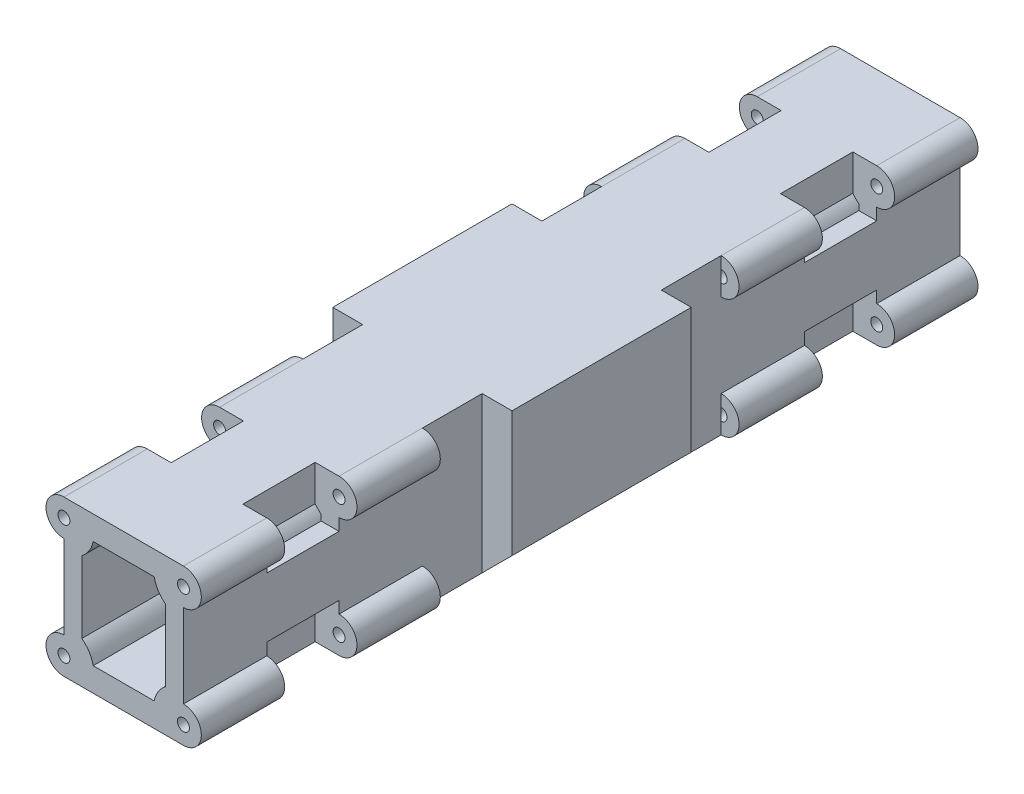
SolidWorks part; units mm, degrees
material "ABS"
ref_plane "Спереди" through (0, 0, 0) normal (0, 0, 1) x (1, 0, 0)
ref_plane "Сверху" through (0, 0, 0) normal (0, 1, 0) x (1, 0, 0)
ref_plane "Справа" through (0, 0, 0) normal (1, 0, 0) x (0, 0, -1)
sketch "Эскиз1" plane through (0, 0, 0) normal (0, 0, 1) x (1, 0, 0)
  line L0 (0, 30.7154) -> (0, -31.2898) construction
  line L2 (15, -13.2872) -> (-15, -13.2872)
  line L3 (15, -13.2872) -> (15, 12.7128)
  line L4 (15, 12.7128) -> (-15, 12.7128)
  line L5 (-15, -13.2872) -> (-15, 12.7128)
  line L6 (15, -13.2872) -> (-15, 12.7128) construction
  line L7 (15, 12.7128) -> (-15, -13.2872) construction
  point P3 (0, -0.2872)
  dimension "D1" = 30
  dimension "D2" = 26
extrude "Бобышка-Вытянуть1" add sketch "Эскиз1" along normal mid plane 130
sketch "Эскиз7" plane through (0, 0, 65) normal (0, 0, 1) x (1, 0, 0)
  line L1 (-15, -13.2872) -> (-10, -13.2872)
  line L2 (-15, -13.2872) -> (-15, 12.7128)
  line L3 (-15, 12.7128) -> (-10, 12.7128)
  line L4 (-10, -13.2872) -> (-10, 12.7128)
  dimension "D1" = 26
  dimension "D2" = 5
extrude "Вырез-Вытянуть5" cut sketch "Эскиз7" against normal blind 50
sketch "Эскиз4" plane through (0, 0, 65) normal (0, 0, 1) x (1, 0, 0)
  line L1 (-10, -13.2872) -> (-10, 12.7128) construction
  line L2 (-15, -13.2872) -> (-10, -13.2872) construction
  circle A0 centre (-10, 9.7128) radius 3
  circle A1 centre (-10, -10.2872) radius 3
  line M8 (-10, 12.7128) -> (-10, -13.2872)
  dimension "D1" = 6
  dimension "D2" = 20
  dimension "D3" = 3
extrude "Бобышка-Вытянуть3" add sketch "Эскиз4" against normal blind 40 contours A1 M8 | A1 M8 | A0 | A0 region at (-8.7268, 9.7128, 65) region at (-8.7268, -10.2872, 65) region at (-11.2732, -10.2872, 65)
sketch "Эскиз5" plane through (-10, 0, 0) normal (-1, 0, 0) x (0, 0, 1)
  line L5 (25, -13.2872) -> (65, -13.2872) construction
  line L6 (38.95, -13.2872) -> (51.05, -13.2872)
  line L11 (38.95, -13.2872) -> (38.95, -5.2872)
  line L12 (38.95, -5.2872) -> (51.05, -5.2872)
  line L13 (51.05, -13.2872) -> (51.05, -5.2872)
  line L19 (65, 6.7128) -> (65, 12.7128) construction
  line L29 (38.95, 4.7128) -> (51.05, 4.7128)
  line L30 (38.95, 4.7128) -> (38.95, 12.7128)
  line L31 (38.95, 12.7128) -> (51.05, 12.7128)
  line L32 (51.05, 4.7128) -> (51.05, 12.7128)
  line L33 (25, 12.7128) -> (65, 12.7128) construction
  dimension "D1" = 12.1
  dimension "D2" = 8
  dimension "D4" = 8
  dimension "D3" = 13.95
extrude "Вырез-Вытянуть3" cut sketch "Эскиз5" against normal mid plane 8
sketch "Эскиз6" plane through (0, 0, 65) normal (0, 0, 1) x (1, 0, 0)
  circle A0 centre (-10, 9.7128) radius 1
  circle A1 centre (-10, -10.2872) radius 1
  dimension "D1" = 2
extrude "Вырез-Вытянуть4" cut sketch "Эскиз6" against normal blind 40
mirror "Зеркальное отражение1" about plane through (0, 0, 0) normal (0, 0, 1) of "Вырез-Вытянуть5", "Вырез-Вытянуть4", "Вырез-Вытянуть3", "Бобышка-Вытянуть3"
mirror "Зеркальное отражение2" about plane through (0, 0, 0) normal (1, 0, 0) of "Зеркальное отражение1"
sketch "Эскиз9" plane through (0, 0, 0) normal (0, 0, 1) x (1, 0, 0)
  line L0 (0, 14.7189) -> (0, -15.9167) construction
  line L1 (-10, 10.7128) -> (-10, 8.7128) construction
  line L2 (10, 10.7128) -> (10, 8.7128) construction
  line L3 (-10, -9.2872) -> (-10, -11.2872) construction
  line L4 (10, -9.2872) -> (10, -11.2872) construction
  line L5 (-7, 5.7128) -> (-7, -6.2872)
  line L6 (-5.101, -9.2872) -> (5.101, -9.2872)
  line L7 (7, -6.2872) -> (7, 5.7128)
  line L8 (-5.101, 8.7128) -> (5.101, 8.7128)
  line L9 (10, 12.7128) -> (-10, 12.7128) construction
  line L10 (-10, -7.2872) -> (-10, 6.7128) construction
  line L11 (-10, -13.2872) -> (10, -13.2872) construction
  circle A0 centre (-10, 9.7128) radius 5
  circle A1 centre (10, 9.7128) radius 5
  circle A2 centre (-10, -10.2872) radius 5
  circle A3 centre (10, -10.2872) radius 5
  dimension "D1" = 10
  dimension "D2" = 4
  dimension "D3" = 3
  dimension "D4" = 4
extrude "Вырез-Вытянуть7" cut sketch "Эскиз9" against normal through all both and the other way through all contours L0 L8 A0 L5 A2 L6 | L8 L0 L6 A3 L7 A1 region at (3.3306, -0.2872, 0) region at (-3.3306, -0.2872, 0)
sketch "Эскиз10" plane through (0, 0, 15) normal (0, 0, 1) x (1, 0, 0)
  line L0 (15, 12.7128) -> (15, -13.2872) construction
  line L2 (-10, -13.2872) -> (10, -13.2872) construction
  line L4 (-15, 12.7128) -> (-15, -13.2872) construction
  line L5 (15, 12.7128) -> (15, -8.2872)
  line L6 (-15, -8.2872) -> (-10, -13.2872)
  line L7 (-10, -13.2872) -> (10, -13.2872)
  line L8 (15, -8.2872) -> (10, -13.2872)
  line L9 (-15, 12.7128) -> (-15, -8.2872)
  line L10 (-15, -8.2872) -> (-15, -13.2872)
  line L11 (-15, -13.2872) -> (-10, -13.2872)
  line L12 (10, -13.2872) -> (15, -13.2872)
  line L13 (15, -13.2872) -> (15, -8.2872)
  line M4 (-15, 12.7128) -> (-15, -13.2872)
  line M5 (-15, -13.2872) -> (-10, -13.2872)
extrude "Вырез-Вытянуть8" cut sketch "Эскиз10" against normal up to next contours L6 M4 M5 | L12 L13 L8 region at (13.3333, -11.6205, 15) region at (-13.3333, -11.6205, 15)
equation "\"D4@Эскиз5\"=\"D2@Эскиз5\""
equation "\"D4@Эскиз9\"=\"D2@Эскиз9\""
